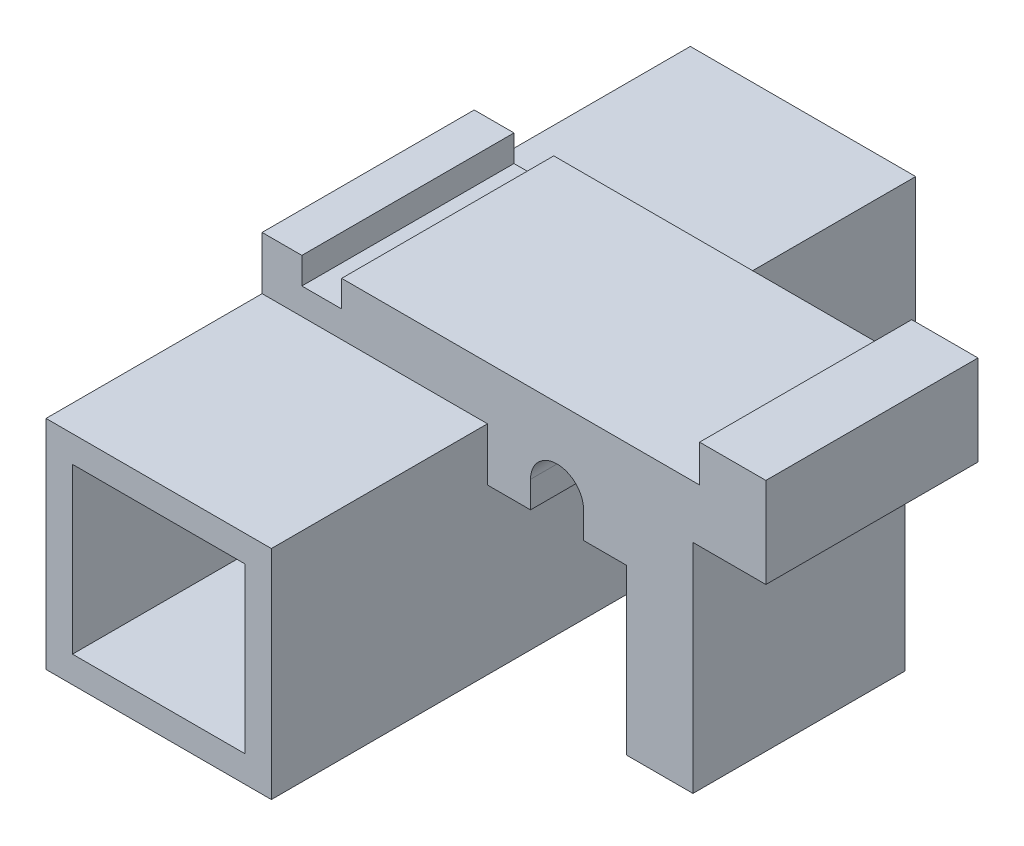
SolidWorks part; units mm, degrees
material "PBT General Purpose"
ref_plane "Alzado" through (0, 0, 0) normal (0, 0, 1) x (1, 0, 0)
ref_plane "Planta" through (0, 0, 0) normal (0, 1, 0) x (1, 0, 0)
ref_plane "Vista lateral" through (0, 0, 0) normal (1, 0, 0) x (0, 0, -1)
sketch "Croquis1" plane through (0, 0, 0) normal (0, 0, 1) x (1, 0, 0)
  line L0 (-1, 1) -> (-7.5, 1)
  line L1 (0, 0) -> (-8.5, 0)
  line L2 (0, 0) -> (0, 8.2)
  line L3 (0, 8.2) -> (-8.5, 8.2)
  line L4 (-8.5, 0) -> (-8.5, 8.2)
  line L5 (-7.5, 1) -> (-7.5, 7.2)
  line L6 (-1, 7.2) -> (-7.5, 7.2)
  line L7 (-1, 1) -> (-1, 7.2)
  dimension "D1" = 8.2
  dimension "D2" = 8.5
  dimension "D3" = 1
extrude "Saliente-Extruir1" add sketch "Croquis1" along normal blind 24.3
sketch "Croquis2" plane through (-8.5, 0, 0) normal (-1, 0, 0) x (0, 0, 1)
  line L0 (0, 4.1) -> (24.3, 4.1) construction
  line L1 (0, 8.2) -> (0, 0) construction
  line L2 (24.3, 8.2) -> (24.3, 0) construction
  line L3 (12.15, 0) -> (12.15, 8.2) construction
  line L4 (24.3, 0) -> (0, 0) construction
  line L5 (24.3, 8.2) -> (0, 8.2) construction
  line L6 (12.15, 8.2) -> (12.15, 10.2)
  line L7 (16.15, 10.2) -> (8.15, 10.2)
  line L8 (8.15, 10.2) -> (8.15, 8.2)
  line L9 (16.15, 8.2) -> (8.15, 8.2)
  line L10 (16.15, 10.2) -> (16.15, 8.2)
  line M4 (24.3, 8.2) -> (0, 8.2)
  dimension "D1" = 2
  dimension "D2" = 4
extrude "Saliente-Extruir2" add sketch "Croquis2" against normal blind 19 contours L7 L8 L6 M4 | L10 L7 L6 M4 region at (-8.5, 9.2, 10.15) region at (-8.5, 9.2, 14.15)
sketch "Croquis3" plane through (0, 10.2, 0) normal (0, 1, 0) x (1, 0, 0)
  line L0 (10.5, -8.15) -> (10.5, -16.15)
  line L1 (10.5, -16.15) -> (8, -16.15)
  line L2 (10.5, -16.15) -> (-8.5, -16.15) construction
  line L3 (8, -16.15) -> (8, -8.15)
  line L4 (10.5, -8.15) -> (-8.5, -8.15) construction
  line L5 (8, -8.15) -> (10.5, -8.15)
  dimension "D1" = 2.5
extrude "Saliente-Extruir3" add sketch "Croquis3" along normal blind 1.4
sketch "Croquis4" plane through (0, 8.2, 0) normal (0, -1, 0) x (1, 0, 0)
  line L0 (10.5, 12.15) -> (0, 12.15) construction
  line L1 (10.5, 16.15) -> (10.5, 8.15) construction
  line L2 (0, 16.15) -> (0, 8.15) construction
  line L3 (5.25, 16.15) -> (5.25, 8.15) construction
  line L4 (10.5, 16.15) -> (0, 16.15) construction
  line L5 (10.5, 8.15) -> (0, 8.15) construction
  line L6 (10.5, 16.15) -> (7.75, 16.15)
  line L7 (7.75, 16.15) -> (7.75, 8.15)
  line L8 (10.5, 8.15) -> (7.75, 8.15)
  line L9 (7.75, 16.15) -> (0, 16.15)
  line L10 (0, 16.15) -> (0, 8.15)
  line L11 (0, 8.15) -> (7.75, 8.15)
  line M1 (10.5, 16.15) -> (0, 16.15)
  line M2 (0, 16.15) -> (0, 8.15)
  line M3 (0, 8.15) -> (10.5, 8.15)
  dimension "D1" = 2.75
extrude "Saliente-Extruir4" add sketch "Croquis4" along normal blind 2 contours L7 M1 M2 M3 region at (3.875, 8.2, 12.15)
sketch "Croquis5" plane through (0, 6.2, 0) normal (0, -1, 0) x (1, 0, 0)
  line L0 (7.75, 16.15) -> (7.75, 8.15)
  line L1 (7.75, 8.15) -> (5.25, 8.15)
  line L2 (0, 8.15) -> (7.75, 8.15) construction
  line L3 (5.25, 8.15) -> (5.25, 16.15)
  line L4 (7.75, 16.15) -> (0, 16.15) construction
  line L5 (5.25, 16.15) -> (7.75, 16.15)
  dimension "D1" = 2.5
extrude "Saliente-Extruir5" add sketch "Croquis5" along normal blind 6.2
sketch "Croquis6" plane through (0, 0, 16.15) normal (0, 0, 1) x (1, 0, 0)
  line L0 (2.625, 6.2) -> (2.625, 8.2)
  line L1 (5.25, 6.2) -> (0, 6.2) construction
  line L2 (0, 6.2) -> (1.625, 6.2)
  line L3 (0, 8.2) -> (5.25, 8.2)
  line L4 (3.625, 7.2) -> (3.625, 6.2)
  line L5 (1.625, 7.2) -> (1.625, 6.2)
  line L6 (3.625, 6.2) -> (5.25, 6.2)
  line L7 (0, 6.2) -> (5.25, 6.2) construction
  arc A0 (3.625, 7.2) -> (1.625, 7.2) centre (2.625, 7.2) ccw
  line M4 (0, 6.2) -> (5.25, 6.2)
  dimension "D1" = 2
extrude "Cortar-Extruir1" cut sketch "Croquis6" against normal blind 8 contours L0 A0 L5 M4 | L4 A0 L0 M4 region at (2.1583, 7.1067, 16.15) region at (3.0917, 7.1067, 16.15)
sketch "Croquis7" plane through (0, 10.2, 0) normal (0, 1, 0) x (1, 0, 0)
  line L1 (-7, -16.15) -> (-5.5, -16.15)
  line L3 (-7, -8.15) -> (-7, -16.15)
  line L4 (-5.5, -8.15) -> (-5.5, -16.15)
  line L5 (-7, -8.15) -> (-5.5, -8.15)
extrude "Cortar-Extruir2" cut sketch "Croquis7" against normal blind 1
sketch "Croquis8" plane through (-8.5, 0, 0) normal (-1, 0, 0) x (0, 0, 1)
  line L0 (0, 4.1) -> (24.3, 4.1) construction
  line L1 (0, 8.2) -> (0, 0) construction
  line L2 (24.3, 8.2) -> (24.3, 0) construction
  line L3 (0, 5.6) -> (24.3, 5.6) construction
  line L4 (0, 7.1) -> (24.3, 7.1) construction
  line L5 (0, 2.6) -> (24.3, 2.6) construction
  line L6 (0, 1.1) -> (24.3, 1.1) construction
  text T0 "Nur Sicherung 250V" font "Century Gothic" height in points 4
  text T1 "User Only With A 250V Fuse" font "Century Gothic" height in points 4
  text T2 "Employer Uniquement Avec" font "Century Gothic" height in points 4
  text T3 "Fusible de 250V" font "Century Gothic" height in points 4
  dimension "D1" = 1.5
  dimension "D2" = 1.5
  dimension "D3" = 1.5
  dimension "D4" = 1.5
extrude "Cortar-Extruir3" cut sketch "Croquis8" against normal blind 0.5
